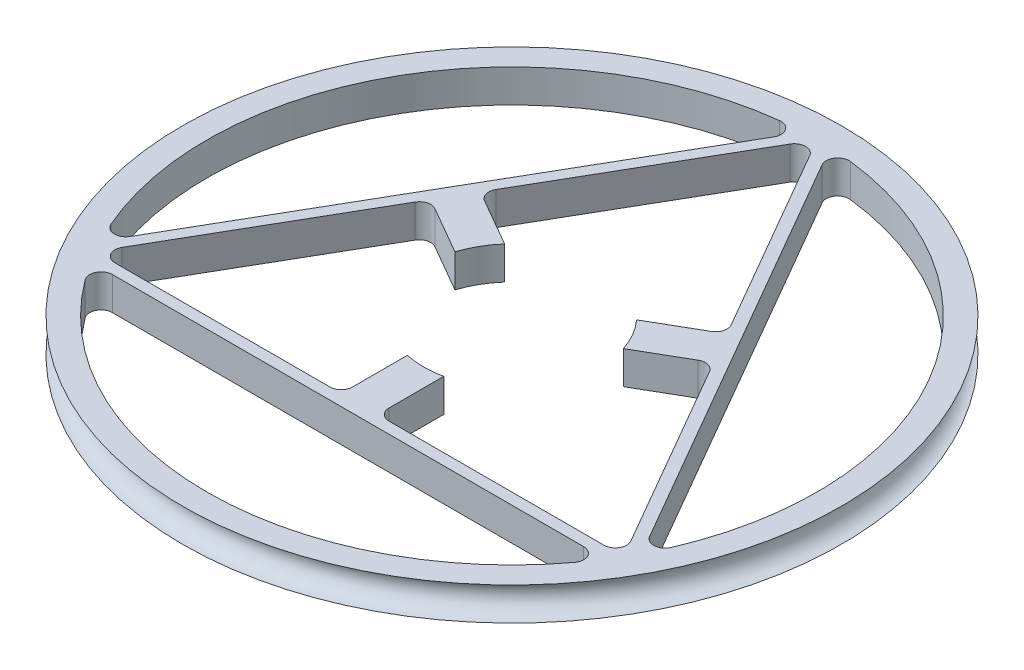
SolidWorks part; units mm, degrees
ref_plane "Front Plane" through (0, 0, 0) normal (0, 0, 1) x (1, 0, 0)
ref_plane "Top Plane" through (0, 0, 0) normal (0, 1, 0) x (1, 0, 0)
ref_plane "Right Plane" through (0, 0, 0) normal (1, 0, 0) x (0, 0, -1)
sketch "Sketch1" plane through (0, 0, 0) normal (0, 1, 0) x (1, 0, 0)
  line L0 (-1.0999, 32.1463) -> (-13.1159, 11.3339)
  line L1 (-27.2896, -17.0256) -> (-3.302, -17.0256)
  line L2 (28.3894, -15.1206) -> (16.3956, 5.6532)
  line L3 (-2.6935, 31.9261) -> (-28.9955, -13.6304)
  line L4 (2.6935, 31.9261) -> (28.9955, -13.6304)
  line L5 (-26.3021, -18.2956) -> (26.3021, -18.2956)
  line L6 (3.302, -17.0256) -> (27.2896, -17.0256)
  line L7 (-12.651, 9.5991) -> (-7.3683, 6.5491)
  line L8 (-14.683, 6.0795) -> (-9.3841, 3.0202)
  line L9 (12.6288, 9.6376) -> (7.338, 6.583)
  line L10 (9.37, 3.0634) -> (14.6608, 6.1181)
  line L11 (13.0936, 11.3724) -> (1.0999, 32.1463)
  line L12 (-2.032, -9.6464) -> (-2.032, -15.7556)
  line L13 (2.032, -15.7556) -> (2.032, -9.6464)
  line L14 (-16.4179, 5.6147) -> (-28.3894, -15.1206)
  circle A0 centre (0, 0) radius 36.7851
  arc A1 (-3.9403, 33.8225) -> (-31.2613, -13.4989) centre (0, 0) ccw
  arc A2 (-27.321, -20.3236) -> (27.321, -20.3236) centre (0, 0) ccw
  arc A3 (31.2613, -13.4989) -> (3.9403, 33.8225) centre (0, 0) ccw
  arc A4 (27.321, -20.3236) -> (26.3021, -18.2956) centre (26.3021, -19.5656) ccw
  arc A5 (27.2896, -17.0256) -> (28.3894, -15.1206) centre (27.2896, -15.7556) ccw
  arc A6 (28.9955, -13.6304) -> (31.2613, -13.4989) centre (30.0954, -12.9954) ccw
  arc A7 (-31.2613, -13.4989) -> (-28.9955, -13.6304) centre (-30.0954, -12.9954) ccw
  arc A8 (-27.321, -20.3236) -> (-26.3021, -18.2956) centre (-26.3021, -19.5656) cw
  arc A9 (-27.2896, -17.0256) -> (-28.3894, -15.1206) centre (-27.2896, -15.7556) cw
  arc A10 (1.0999, 32.1463) -> (-1.0999, 32.1463) centre (0, 31.5113) ccw
  arc A11 (2.6935, 31.9261) -> (3.9403, 33.8225) centre (3.7933, 32.5611) cw
  arc A12 (-2.6935, 31.9261) -> (-3.9403, 33.8225) centre (-3.7933, 32.5611) ccw
  arc A13 (-7.3683, 6.5491) -> (-9.3841, 3.0202) centre (0, 0) ccw
  arc A14 (-2.032, -9.6464) -> (2.032, -9.6464) centre (0, 0) ccw
  arc A15 (9.37, 3.0634) -> (7.338, 6.583) centre (0, 0) ccw
  arc A16 (3.302, -17.0256) -> (2.032, -15.7556) centre (3.302, -15.7556) cw
  arc A17 (16.3956, 5.6532) -> (14.6608, 6.1181) centre (15.2958, 5.0182) ccw
  arc A18 (13.0936, 11.3724) -> (12.6288, 9.6376) centre (11.9938, 10.7374) cw
  arc A19 (-12.651, 9.5991) -> (-13.1159, 11.3339) centre (-12.016, 10.6989) cw
  arc A20 (-14.683, 6.0795) -> (-16.4179, 5.6147) centre (-15.318, 4.9797) ccw
  arc A21 (-3.302, -17.0256) -> (-2.032, -15.7556) centre (-3.302, -15.7556) ccw
  point P12 (28.7186, -18.2956)
  point P17 (29.4893, -17.0256)
  point P20 (30.2038, -15.7232)
  point P25 (-28.7186, -18.2956)
  point P28 (-29.4893, -17.0256)
  point P31 (0, 34.0513)
  point P47 (2.032, -17.0256)
  point P55 (13.7286, 10.2726)
  point P60 (-15.7829, 6.7145)
  dimension "D1" = 1.27
  dimension "D4" = 1.27
  dimension "D5" = 4.064
  dimension "D6" = 1.27
  dimension "D8" = 1.27
  dimension "D2" = 1.27
  dimension "D3" = 1.27
  dimension "D7" = 4.064
  dimension "D9" = 4.064
extrude "Boss-Extrude1" add sketch "Sketch1" along normal blind 3.683
sketch "Sketch2" plane through (0, 0, 0) normal (0, 0, 1) x (1, 0, 0)
  line L1 (36.7851, 0) -> (36.7851, 3.683) construction
  line L2 (0, 0) -> (0, 17.4834) construction
  circle A0 centre (36.7851, 1.8415) radius 1.8415
sketch "Sketch4" plane through (0, 0, 0) normal (1, 0, 0) x (0, 0, -1)
  line L0 (0, 1.1871) -> (0, 9.1244) construction
  line L1 (0, 3.683) -> (0, 0) construction
  line L2 (0, 9.1244) -> (0, -8.0635) construction
ref_axis "Axis1" through (0, 9.1244, 0) along (0, -1, 0)
revolve "Cut-Revolve2" cut sketch "Sketch2" angle 360 about L2
